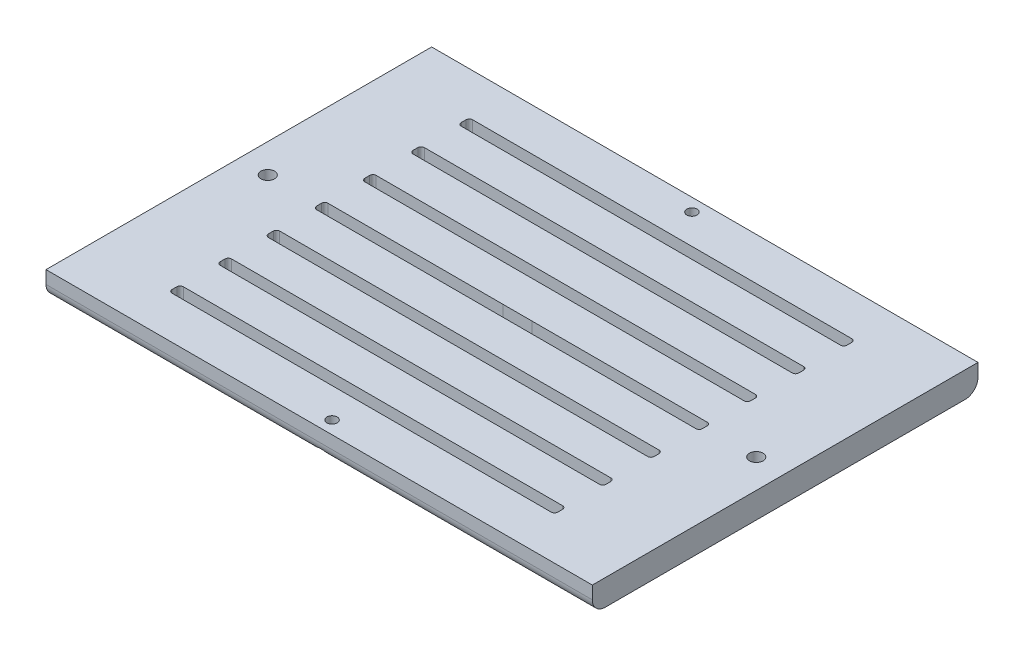
SolidWorks part; units mm, degrees
ref_plane "Ön Düzlem" through (0, 0, 0) normal (0, 0, 1) x (1, 0, 0)
ref_plane "Üst Düzlem" through (0, 0, 0) normal (0, 1, 0) x (1, 0, 0)
ref_plane "Sağ Düzlem" through (0, 0, 0) normal (1, 0, 0) x (0, 0, -1)
sketch "Çizim1" plane through (0, 0, 0) normal (0, 0, 1) x (1, 0, 0)
  line L1 (-85, -4) -> (85, -4)
  line L2 (-85, -4) -> (-85, 4)
  line L3 (-85, 4) -> (85, 4)
  line L4 (85, -4) -> (85, 4)
  line L5 (-85, -4) -> (85, 4) construction
  line L6 (-85, 4) -> (85, -4) construction
  point P0 (0, 0)
  dimension "D1" = 170
  dimension "D2" = 8
extrude "Yükseklik-Ekstrüzyon1" add sketch "Çizim1" along normal mid plane 120 contours L3 L4 L1 L2
sketch "Çizim2" plane through (0, 0, 0) normal (0, 1, 0) x (1, 0, 0)
  line L0 (-85, 60) -> (85, 60) construction
  line L1 (0, 56) -> (0, -56) construction
  line L2 (85, -60) -> (85, 60) construction
  line L3 (-76, 0) -> (76, 0) construction
  line L4 (-85, -60) -> (-85, 60) construction
  circle A0 centre (0, 56) radius 1.6
  circle A1 centre (0, -56) radius 1.6
  circle A2 centre (-76, 0) radius 2.1
  circle A3 centre (76, 0) radius 2.1
  point P4 (0, 0)
  point P8 (0, 60)
  point P13 (0, 0)
  point P16 (85, 0)
  dimension "D2" = 3.2
  dimension "D3" = 4.2
  dimension "D1" = 4
  dimension "D4" = 9
extrude "Kes-Ekstrüzyon1" cut sketch "Çizim2" against normal mid plane 10
sketch "Çizim3" plane through (0, -4, 0) normal (0, -1, 0) x (1, 0, 0)
  circle A0 centre (0, -56) radius 3.4
  circle A1 centre (0, 56) radius 3.4
  circle A2 centre (0, -56) radius 1.6 construction
  circle A3 centre (0, 56) radius 1.6 construction
  circle A4 centre (-76, 0) radius 4.4 construction
  circle A5 centre (76, 0) radius 4.4 construction
  circle A6 centre (76, 0) radius 2.1 construction
  circle A7 centre (-76, 0) radius 2.1 construction
  dimension "D1" = 6.8
  dimension "D2" = 8.8
extrude "Kes-Ekstrüzyon2" cut sketch "Çizim3" against normal blind 2.7
sketch "Çizim4" plane through (0, -4, 0) normal (0, -1, 0) x (1, 0, 0)
  circle A0 centre (-76, 0) radius 4.4
  circle A1 centre (76, 0) radius 4.4
  circle A3 centre (-76, 0) radius 4.4 construction
  circle A4 centre (76, 0) radius 4.4 construction
extrude "Kes-Ekstrüzyon3" cut sketch "Çizim4" against normal blind 3.5
fillet "Radyus1" radius 4 2 edges at (0, -4, -60) (0, -4, 60)
sketch "Çizim5" plane through (0, 0, 0) normal (0, 1, 0) x (1, 0, 0)
  line L0 (0, -5) -> (0, 5) construction
  line L1 (-7.5, 1) -> (7.5, 1)
  line L2 (-7.5, 1) -> (-7.5, -1)
  line L3 (-7.5, -1) -> (7.5, -1)
  line L4 (7.5, 1) -> (7.5, -1)
  line L5 (-7.5, 1) -> (7.5, -1) construction
  line L6 (-7.5, -1) -> (7.5, 1) construction
  line L7 (32.5, 1) -> (32.5, -1)
  line L8 (17.5, -1) -> (32.5, -1)
  line L9 (17.5, 1) -> (17.5, -1)
  line L10 (17.5, 1) -> (32.5, 1)
  line L11 (57.5, 1) -> (57.5, -1)
  line L12 (42.5, -1) -> (57.5, -1)
  line L13 (42.5, 1) -> (42.5, -1)
  line L14 (42.5, 1) -> (57.5, 1)
  line L15 (32.5, 11) -> (32.5, 9)
  line L16 (17.5, 9) -> (32.5, 9)
  line L17 (17.5, 11) -> (17.5, 9)
  line L18 (17.5, 11) -> (32.5, 11)
  line L19 (57.5, 11) -> (57.5, 9)
  line L20 (42.5, 9) -> (57.5, 9)
  line L21 (42.5, 11) -> (42.5, 9)
  line L22 (42.5, 11) -> (57.5, 11)
  line L23 (32.5, 21) -> (32.5, 19)
  line L24 (17.5, 19) -> (32.5, 19)
  line L25 (17.5, 21) -> (17.5, 19)
  line L26 (17.5, 21) -> (32.5, 21)
  line L27 (57.5, 21) -> (57.5, 19)
  line L28 (42.5, 19) -> (57.5, 19)
  line L29 (42.5, 21) -> (42.5, 19)
  line L30 (42.5, 21) -> (57.5, 21)
  line L31 (32.5, 31) -> (32.5, 29)
  line L32 (17.5, 29) -> (32.5, 29)
  line L33 (17.5, 31) -> (17.5, 29)
  line L34 (17.5, 31) -> (32.5, 31)
  line L35 (57.5, 31) -> (57.5, 29)
  line L36 (42.5, 29) -> (57.5, 29)
  line L37 (42.5, 31) -> (42.5, 29)
  line L38 (42.5, 31) -> (57.5, 31)
  line L39 (32.5, 41) -> (32.5, 39)
  line L40 (17.5, 39) -> (32.5, 39)
  line L41 (17.5, 41) -> (17.5, 39)
  line L42 (17.5, 41) -> (32.5, 41)
  line L43 (57.5, 41) -> (57.5, 39)
  line L44 (42.5, 39) -> (57.5, 39)
  line L45 (42.5, 41) -> (42.5, 39)
  line L46 (42.5, 41) -> (57.5, 41)
  line L47 (7.5, 11) -> (7.5, 9)
  line L48 (-7.5, 9) -> (7.5, 9)
  line L49 (-7.5, 11) -> (-7.5, 9)
  line L50 (-7.5, 11) -> (7.5, 11)
  line L51 (7.5, 21) -> (7.5, 19)
  line L52 (-7.5, 19) -> (7.5, 19)
  line L53 (-7.5, 21) -> (-7.5, 19)
  line L54 (-7.5, 21) -> (7.5, 21)
  line L55 (7.5, 31) -> (7.5, 29)
  line L56 (-7.5, 29) -> (7.5, 29)
  line L57 (-7.5, 31) -> (-7.5, 29)
  line L58 (-7.5, 31) -> (7.5, 31)
  line L59 (7.5, 41) -> (7.5, 39)
  line L60 (-7.5, 39) -> (7.5, 39)
  line L61 (-7.5, 41) -> (-7.5, 39)
  line L62 (-7.5, 41) -> (7.5, 41)
  line L63 (-17.5, 1) -> (-17.5, -1)
  line L64 (-32.5, -1) -> (-17.5, -1)
  line L65 (-32.5, 1) -> (-32.5, -1)
  line L66 (-32.5, 1) -> (-17.5, 1)
  line L67 (-42.5, 1) -> (-42.5, -1)
  line L68 (-57.5, -1) -> (-42.5, -1)
  line L69 (-57.5, 1) -> (-57.5, -1)
  line L70 (-57.5, 1) -> (-42.5, 1)
  line L71 (-17.5, 11) -> (-17.5, 9)
  line L72 (-32.5, 9) -> (-17.5, 9)
  line L73 (-32.5, 11) -> (-32.5, 9)
  line L74 (-32.5, 11) -> (-17.5, 11)
  line L75 (-42.5, 11) -> (-42.5, 9)
  line L76 (-57.5, 9) -> (-42.5, 9)
  line L77 (-57.5, 11) -> (-57.5, 9)
  line L78 (-57.5, 11) -> (-42.5, 11)
  line L79 (-17.5, 21) -> (-17.5, 19)
  line L80 (-32.5, 19) -> (-17.5, 19)
  line L81 (-32.5, 21) -> (-32.5, 19)
  line L82 (-32.5, 21) -> (-17.5, 21)
  line L83 (-42.5, 21) -> (-42.5, 19)
  line L84 (-57.5, 19) -> (-42.5, 19)
  line L85 (-57.5, 21) -> (-57.5, 19)
  line L86 (-57.5, 21) -> (-42.5, 21)
  line L87 (-17.5, 31) -> (-17.5, 29)
  line L88 (-32.5, 29) -> (-17.5, 29)
  line L89 (-32.5, 31) -> (-32.5, 29)
  line L90 (-32.5, 31) -> (-17.5, 31)
  line L91 (-42.5, 31) -> (-42.5, 29)
  line L92 (-57.5, 29) -> (-42.5, 29)
  line L93 (-57.5, 31) -> (-57.5, 29)
  line L94 (-57.5, 31) -> (-42.5, 31)
  line L95 (-17.5, 41) -> (-17.5, 39)
  line L96 (-32.5, 39) -> (-17.5, 39)
  line L97 (-32.5, 41) -> (-32.5, 39)
  line L98 (-32.5, 41) -> (-17.5, 41)
  line L99 (-42.5, 41) -> (-42.5, 39)
  line L100 (-57.5, 39) -> (-42.5, 39)
  line L101 (-57.5, 41) -> (-57.5, 39)
  line L102 (-57.5, 41) -> (-42.5, 41)
  line L103 (7.5, 11) -> (7.5, 9)
  line L104 (-7.5, 9) -> (7.5, 9)
  line L105 (-7.5, 11) -> (-7.5, 9)
  line L106 (-7.5, 11) -> (7.5, 11)
  line L107 (7.5, 21) -> (7.5, 19)
  line L108 (-7.5, 19) -> (7.5, 19)
  line L109 (-7.5, 21) -> (-7.5, 19)
  line L110 (-7.5, 21) -> (7.5, 21)
  line L111 (7.5, 31) -> (7.5, 29)
  line L112 (-7.5, 29) -> (7.5, 29)
  line L113 (-7.5, 31) -> (-7.5, 29)
  line L114 (-7.5, 31) -> (7.5, 31)
  line L115 (7.5, 41) -> (7.5, 39)
  line L116 (-7.5, 39) -> (7.5, 39)
  line L117 (-7.5, 41) -> (-7.5, 39)
  line L118 (-7.5, 41) -> (7.5, 41)
  line L119 (7.5, -9) -> (7.5, -11)
  line L120 (-7.5, -11) -> (7.5, -11)
  line L121 (-7.5, -9) -> (-7.5, -11)
  line L122 (-7.5, -9) -> (7.5, -9)
  line L123 (32.5, -9) -> (32.5, -11)
  line L124 (17.5, -11) -> (32.5, -11)
  line L125 (17.5, -9) -> (17.5, -11)
  line L126 (17.5, -9) -> (32.5, -9)
  line L127 (57.5, -9) -> (57.5, -11)
  line L128 (42.5, -11) -> (57.5, -11)
  line L129 (42.5, -9) -> (42.5, -11)
  line L130 (42.5, -9) -> (57.5, -9)
  line L131 (32.5, -19) -> (32.5, -21)
  line L132 (17.5, -21) -> (32.5, -21)
  line L133 (17.5, -19) -> (17.5, -21)
  line L134 (17.5, -19) -> (32.5, -19)
  line L135 (57.5, -19) -> (57.5, -21)
  line L136 (42.5, -21) -> (57.5, -21)
  line L137 (42.5, -19) -> (42.5, -21)
  line L138 (42.5, -19) -> (57.5, -19)
  line L139 (32.5, -29) -> (32.5, -31)
  line L140 (17.5, -31) -> (32.5, -31)
  line L141 (17.5, -29) -> (17.5, -31)
  line L142 (17.5, -29) -> (32.5, -29)
  line L143 (57.5, -29) -> (57.5, -31)
  line L144 (42.5, -31) -> (57.5, -31)
  line L145 (42.5, -29) -> (42.5, -31)
  line L146 (42.5, -29) -> (57.5, -29)
  line L147 (32.5, -39) -> (32.5, -41)
  line L148 (17.5, -41) -> (32.5, -41)
  line L149 (17.5, -39) -> (17.5, -41)
  line L150 (17.5, -39) -> (32.5, -39)
  line L151 (57.5, -39) -> (57.5, -41)
  line L152 (42.5, -41) -> (57.5, -41)
  line L153 (42.5, -39) -> (42.5, -41)
  line L154 (42.5, -39) -> (57.5, -39)
  line L155 (7.5, -19) -> (7.5, -21)
  line L156 (-7.5, -21) -> (7.5, -21)
  line L157 (-7.5, -19) -> (-7.5, -21)
  line L158 (-7.5, -19) -> (7.5, -19)
  line L159 (7.5, -29) -> (7.5, -31)
  line L160 (-7.5, -31) -> (7.5, -31)
  line L161 (-7.5, -29) -> (-7.5, -31)
  line L162 (-7.5, -29) -> (7.5, -29)
  line L163 (7.5, -39) -> (7.5, -41)
  line L164 (-7.5, -41) -> (7.5, -41)
  line L165 (-7.5, -39) -> (-7.5, -41)
  line L166 (-7.5, -39) -> (7.5, -39)
  line L167 (-17.5, -9) -> (-17.5, -11)
  line L168 (-32.5, -11) -> (-17.5, -11)
  line L169 (-32.5, -9) -> (-32.5, -11)
  line L170 (-32.5, -9) -> (-17.5, -9)
  line L171 (-42.5, -9) -> (-42.5, -11)
  line L172 (-57.5, -11) -> (-42.5, -11)
  line L173 (-57.5, -9) -> (-57.5, -11)
  line L174 (-57.5, -9) -> (-42.5, -9)
  line L175 (-17.5, -19) -> (-17.5, -21)
  line L176 (-32.5, -21) -> (-17.5, -21)
  line L177 (-32.5, -19) -> (-32.5, -21)
  line L178 (-32.5, -19) -> (-17.5, -19)
  line L179 (-42.5, -19) -> (-42.5, -21)
  line L180 (-57.5, -21) -> (-42.5, -21)
  line L181 (-57.5, -19) -> (-57.5, -21)
  line L182 (-57.5, -19) -> (-42.5, -19)
  line L183 (-17.5, -29) -> (-17.5, -31)
  line L184 (-32.5, -31) -> (-17.5, -31)
  line L185 (-32.5, -29) -> (-32.5, -31)
  line L186 (-32.5, -29) -> (-17.5, -29)
  line L187 (-42.5, -29) -> (-42.5, -31)
  line L188 (-57.5, -31) -> (-42.5, -31)
  line L189 (-57.5, -29) -> (-57.5, -31)
  line L190 (-57.5, -29) -> (-42.5, -29)
  line L191 (-17.5, -39) -> (-17.5, -41)
  line L192 (-32.5, -41) -> (-17.5, -41)
  line L193 (-32.5, -39) -> (-32.5, -41)
  line L194 (-32.5, -39) -> (-17.5, -39)
  line L195 (-42.5, -39) -> (-42.5, -41)
  line L196 (-57.5, -41) -> (-42.5, -41)
  line L197 (-57.5, -39) -> (-57.5, -41)
  line L198 (-57.5, -39) -> (-42.5, -39)
  line L199 (7.5, -19) -> (7.5, -21)
  line L200 (-7.5, -21) -> (7.5, -21)
  line L201 (-7.5, -19) -> (-7.5, -21)
  line L202 (-7.5, -19) -> (7.5, -19)
  line L203 (7.5, -29) -> (7.5, -31)
  line L204 (-7.5, -31) -> (7.5, -31)
  line L205 (-7.5, -29) -> (-7.5, -31)
  line L206 (-7.5, -29) -> (7.5, -29)
  line L207 (7.5, -39) -> (7.5, -41)
  line L208 (-7.5, -41) -> (7.5, -41)
  line L209 (-7.5, -39) -> (-7.5, -41)
  line L210 (-7.5, -39) -> (7.5, -39)
  line L211 (-42.5, -35) -> (-32.5, -35) construction
  line L212 (-35.4793, -35) -> (-36.4896, -33.25)
  line L213 (-36.4896, -33.25) -> (-38.5104, -33.25)
  line L214 (-38.5104, -33.25) -> (-39.5207, -35)
  line L215 (-39.5207, -35) -> (-38.5104, -36.75)
  line L216 (-38.5104, -36.75) -> (-36.4896, -36.75)
  line L217 (-36.4896, -36.75) -> (-35.4793, -35)
  line L218 (-11.4896, -36.75) -> (-10.4793, -35)
  line L219 (-13.5104, -36.75) -> (-11.4896, -36.75)
  line L220 (-14.5207, -35) -> (-13.5104, -36.75)
  line L221 (-13.5104, -33.25) -> (-14.5207, -35)
  line L222 (-11.4896, -33.25) -> (-13.5104, -33.25)
  line L223 (-10.4793, -35) -> (-11.4896, -33.25)
  line L224 (13.5104, -36.75) -> (14.5207, -35)
  line L225 (11.4896, -36.75) -> (13.5104, -36.75)
  line L226 (10.4793, -35) -> (11.4896, -36.75)
  line L227 (11.4896, -33.25) -> (10.4793, -35)
  line L228 (13.5104, -33.25) -> (11.4896, -33.25)
  line L229 (14.5207, -35) -> (13.5104, -33.25)
  line L230 (38.5104, -36.75) -> (39.5207, -35)
  line L231 (36.4896, -36.75) -> (38.5104, -36.75)
  line L232 (35.4793, -35) -> (36.4896, -36.75)
  line L233 (36.4896, -33.25) -> (35.4793, -35)
  line L234 (38.5104, -33.25) -> (36.4896, -33.25)
  line L235 (39.5207, -35) -> (38.5104, -33.25)
  line L236 (-11.4896, -26.75) -> (-10.4793, -25)
  line L237 (-13.5104, -26.75) -> (-11.4896, -26.75)
  line L238 (-14.5207, -25) -> (-13.5104, -26.75)
  line L239 (-13.5104, -23.25) -> (-14.5207, -25)
  line L240 (-11.4896, -23.25) -> (-13.5104, -23.25)
  line L241 (-10.4793, -25) -> (-11.4896, -23.25)
  line L242 (13.5104, -26.75) -> (14.5207, -25)
  line L243 (11.4896, -26.75) -> (13.5104, -26.75)
  line L244 (10.4793, -25) -> (11.4896, -26.75)
  line L245 (11.4896, -23.25) -> (10.4793, -25)
  line L246 (13.5104, -23.25) -> (11.4896, -23.25)
  line L247 (14.5207, -25) -> (13.5104, -23.25)
  line L248 (38.5104, -26.75) -> (39.5207, -25)
  line L249 (36.4896, -26.75) -> (38.5104, -26.75)
  line L250 (35.4793, -25) -> (36.4896, -26.75)
  line L251 (36.4896, -23.25) -> (35.4793, -25)
  line L252 (38.5104, -23.25) -> (36.4896, -23.25)
  line L253 (39.5207, -25) -> (38.5104, -23.25)
  line L254 (-11.4896, -16.75) -> (-10.4793, -15)
  line L255 (-13.5104, -16.75) -> (-11.4896, -16.75)
  line L256 (-14.5207, -15) -> (-13.5104, -16.75)
  line L257 (-13.5104, -13.25) -> (-14.5207, -15)
  line L258 (-11.4896, -13.25) -> (-13.5104, -13.25)
  line L259 (-10.4793, -15) -> (-11.4896, -13.25)
  line L260 (13.5104, -16.75) -> (14.5207, -15)
  line L261 (11.4896, -16.75) -> (13.5104, -16.75)
  line L262 (10.4793, -15) -> (11.4896, -16.75)
  line L263 (11.4896, -13.25) -> (10.4793, -15)
  line L264 (13.5104, -13.25) -> (11.4896, -13.25)
  line L265 (14.5207, -15) -> (13.5104, -13.25)
  line L266 (38.5104, -16.75) -> (39.5207, -15)
  line L267 (36.4896, -16.75) -> (38.5104, -16.75)
  line L268 (35.4793, -15) -> (36.4896, -16.75)
  line L269 (36.4896, -13.25) -> (35.4793, -15)
  line L270 (38.5104, -13.25) -> (36.4896, -13.25)
  line L271 (39.5207, -15) -> (38.5104, -13.25)
  line L272 (-11.4896, -6.75) -> (-10.4793, -5)
  line L273 (-13.5104, -6.75) -> (-11.4896, -6.75)
  line L274 (-14.5207, -5) -> (-13.5104, -6.75)
  line L275 (-13.5104, -3.25) -> (-14.5207, -5)
  line L276 (-11.4896, -3.25) -> (-13.5104, -3.25)
  line L277 (-10.4793, -5) -> (-11.4896, -3.25)
  line L278 (13.5104, -6.75) -> (14.5207, -5)
  line L279 (11.4896, -6.75) -> (13.5104, -6.75)
  line L280 (10.4793, -5) -> (11.4896, -6.75)
  line L281 (11.4896, -3.25) -> (10.4793, -5)
  line L282 (13.5104, -3.25) -> (11.4896, -3.25)
  line L283 (14.5207, -5) -> (13.5104, -3.25)
  line L284 (38.5104, -6.75) -> (39.5207, -5)
  line L285 (36.4896, -6.75) -> (38.5104, -6.75)
  line L286 (35.4793, -5) -> (36.4896, -6.75)
  line L287 (36.4896, -3.25) -> (35.4793, -5)
  line L288 (38.5104, -3.25) -> (36.4896, -3.25)
  line L289 (39.5207, -5) -> (38.5104, -3.25)
  line L290 (-11.4896, 3.25) -> (-10.4793, 5)
  line L291 (-13.5104, 3.25) -> (-11.4896, 3.25)
  line L292 (-14.5207, 5) -> (-13.5104, 3.25)
  line L293 (-13.5104, 6.75) -> (-14.5207, 5)
  line L294 (-11.4896, 6.75) -> (-13.5104, 6.75)
  line L295 (-10.4793, 5) -> (-11.4896, 6.75)
  line L296 (13.5104, 3.25) -> (14.5207, 5)
  line L297 (11.4896, 3.25) -> (13.5104, 3.25)
  line L298 (10.4793, 5) -> (11.4896, 3.25)
  line L299 (11.4896, 6.75) -> (10.4793, 5)
  line L300 (13.5104, 6.75) -> (11.4896, 6.75)
  line L301 (14.5207, 5) -> (13.5104, 6.75)
  line L302 (38.5104, 3.25) -> (39.5207, 5)
  line L303 (36.4896, 3.25) -> (38.5104, 3.25)
  line L304 (35.4793, 5) -> (36.4896, 3.25)
  line L305 (36.4896, 6.75) -> (35.4793, 5)
  line L306 (38.5104, 6.75) -> (36.4896, 6.75)
  line L307 (39.5207, 5) -> (38.5104, 6.75)
  line L308 (-11.4896, 13.25) -> (-10.4793, 15)
  line L309 (-13.5104, 13.25) -> (-11.4896, 13.25)
  line L310 (-14.5207, 15) -> (-13.5104, 13.25)
  line L311 (-13.5104, 16.75) -> (-14.5207, 15)
  line L312 (-11.4896, 16.75) -> (-13.5104, 16.75)
  line L313 (-10.4793, 15) -> (-11.4896, 16.75)
  line L314 (13.5104, 13.25) -> (14.5207, 15)
  line L315 (11.4896, 13.25) -> (13.5104, 13.25)
  line L316 (10.4793, 15) -> (11.4896, 13.25)
  line L317 (11.4896, 16.75) -> (10.4793, 15)
  line L318 (13.5104, 16.75) -> (11.4896, 16.75)
  line L319 (14.5207, 15) -> (13.5104, 16.75)
  line L320 (38.5104, 13.25) -> (39.5207, 15)
  line L321 (36.4896, 13.25) -> (38.5104, 13.25)
  line L322 (35.4793, 15) -> (36.4896, 13.25)
  line L323 (36.4896, 16.75) -> (35.4793, 15)
  line L324 (38.5104, 16.75) -> (36.4896, 16.75)
  line L325 (39.5207, 15) -> (38.5104, 16.75)
  line L326 (-11.4896, 23.25) -> (-10.4793, 25)
  line L327 (-13.5104, 23.25) -> (-11.4896, 23.25)
  line L328 (-14.5207, 25) -> (-13.5104, 23.25)
  line L329 (-13.5104, 26.75) -> (-14.5207, 25)
  line L330 (-11.4896, 26.75) -> (-13.5104, 26.75)
  line L331 (-10.4793, 25) -> (-11.4896, 26.75)
  line L332 (13.5104, 23.25) -> (14.5207, 25)
  line L333 (11.4896, 23.25) -> (13.5104, 23.25)
  line L334 (10.4793, 25) -> (11.4896, 23.25)
  line L335 (11.4896, 26.75) -> (10.4793, 25)
  line L336 (13.5104, 26.75) -> (11.4896, 26.75)
  line L337 (14.5207, 25) -> (13.5104, 26.75)
  line L338 (38.5104, 23.25) -> (39.5207, 25)
  line L339 (36.4896, 23.25) -> (38.5104, 23.25)
  line L340 (35.4793, 25) -> (36.4896, 23.25)
  line L341 (36.4896, 26.75) -> (35.4793, 25)
  line L342 (38.5104, 26.75) -> (36.4896, 26.75)
  line L343 (39.5207, 25) -> (38.5104, 26.75)
  line L344 (-11.4896, 33.25) -> (-10.4793, 35)
  line L345 (-13.5104, 33.25) -> (-11.4896, 33.25)
  line L346 (-14.5207, 35) -> (-13.5104, 33.25)
  line L347 (-13.5104, 36.75) -> (-14.5207, 35)
  line L348 (-11.4896, 36.75) -> (-13.5104, 36.75)
  line L349 (-10.4793, 35) -> (-11.4896, 36.75)
  line L350 (13.5104, 33.25) -> (14.5207, 35)
  line L351 (11.4896, 33.25) -> (13.5104, 33.25)
  line L352 (10.4793, 35) -> (11.4896, 33.25)
  line L353 (11.4896, 36.75) -> (10.4793, 35)
  line L354 (13.5104, 36.75) -> (11.4896, 36.75)
  line L355 (14.5207, 35) -> (13.5104, 36.75)
  line L356 (38.5104, 33.25) -> (39.5207, 35)
  line L357 (36.4896, 33.25) -> (38.5104, 33.25)
  line L358 (35.4793, 35) -> (36.4896, 33.25)
  line L359 (36.4896, 36.75) -> (35.4793, 35)
  line L360 (38.5104, 36.75) -> (36.4896, 36.75)
  line L361 (39.5207, 35) -> (38.5104, 36.75)
  line L362 (-36.4896, -26.75) -> (-35.4793, -25)
  line L363 (-38.5104, -26.75) -> (-36.4896, -26.75)
  line L364 (-39.5207, -25) -> (-38.5104, -26.75)
  line L365 (-38.5104, -23.25) -> (-39.5207, -25)
  line L366 (-36.4896, -23.25) -> (-38.5104, -23.25)
  line L367 (-35.4793, -25) -> (-36.4896, -23.25)
  line L368 (-36.4896, -16.75) -> (-35.4793, -15)
  line L369 (-38.5104, -16.75) -> (-36.4896, -16.75)
  line L370 (-39.5207, -15) -> (-38.5104, -16.75)
  line L371 (-38.5104, -13.25) -> (-39.5207, -15)
  line L372 (-36.4896, -13.25) -> (-38.5104, -13.25)
  line L373 (-35.4793, -15) -> (-36.4896, -13.25)
  line L374 (-36.4896, -6.75) -> (-35.4793, -5)
  line L375 (-38.5104, -6.75) -> (-36.4896, -6.75)
  line L376 (-39.5207, -5) -> (-38.5104, -6.75)
  line L377 (-38.5104, -3.25) -> (-39.5207, -5)
  line L378 (-36.4896, -3.25) -> (-38.5104, -3.25)
  line L379 (-35.4793, -5) -> (-36.4896, -3.25)
  line L380 (-36.4896, 3.25) -> (-35.4793, 5)
  line L381 (-38.5104, 3.25) -> (-36.4896, 3.25)
  line L382 (-39.5207, 5) -> (-38.5104, 3.25)
  line L383 (-38.5104, 6.75) -> (-39.5207, 5)
  line L384 (-36.4896, 6.75) -> (-38.5104, 6.75)
  line L385 (-35.4793, 5) -> (-36.4896, 6.75)
  line L386 (-36.4896, 13.25) -> (-35.4793, 15)
  line L387 (-38.5104, 13.25) -> (-36.4896, 13.25)
  line L388 (-39.5207, 15) -> (-38.5104, 13.25)
  line L389 (-38.5104, 16.75) -> (-39.5207, 15)
  line L390 (-36.4896, 16.75) -> (-38.5104, 16.75)
  line L391 (-35.4793, 15) -> (-36.4896, 16.75)
  line L392 (-36.4896, 23.25) -> (-35.4793, 25)
  line L393 (-38.5104, 23.25) -> (-36.4896, 23.25)
  line L394 (-39.5207, 25) -> (-38.5104, 23.25)
  line L395 (-38.5104, 26.75) -> (-39.5207, 25)
  line L396 (-36.4896, 26.75) -> (-38.5104, 26.75)
  line L397 (-35.4793, 25) -> (-36.4896, 26.75)
  line L398 (-36.4896, 33.25) -> (-35.4793, 35)
  line L399 (-38.5104, 33.25) -> (-36.4896, 33.25)
  line L400 (-39.5207, 35) -> (-38.5104, 33.25)
  line L401 (-38.5104, 36.75) -> (-39.5207, 35)
  line L402 (-36.4896, 36.75) -> (-38.5104, 36.75)
  line L403 (-35.4793, 35) -> (-36.4896, 36.75)
  circle A0 centre (0, -5) radius 1.75
  circle A1 centre (0, 5) radius 1.75
  circle A2 centre (25, 5) radius 1.75
  circle A3 centre (50, 5) radius 1.75
  circle A4 centre (25, 15) radius 1.75
  circle A5 centre (50, 15) radius 1.75
  circle A6 centre (25, 25) radius 1.75
  circle A7 centre (50, 25) radius 1.75
  circle A8 centre (25, 35) radius 1.75
  circle A9 centre (50, 35) radius 1.75
  circle A10 centre (25, 45) radius 1.75
  circle A11 centre (50, 45) radius 1.75
  circle A12 centre (0, 15) radius 1.75
  circle A13 centre (0, 25) radius 1.75
  circle A14 centre (0, 35) radius 1.75
  circle A15 centre (0, 45) radius 1.75
  circle A16 centre (-25, 5) radius 1.75
  circle A17 centre (-50, 5) radius 1.75
  circle A18 centre (-25, 15) radius 1.75
  circle A19 centre (-50, 15) radius 1.75
  circle A20 centre (-25, 25) radius 1.75
  circle A21 centre (-50, 25) radius 1.75
  circle A22 centre (-25, 35) radius 1.75
  circle A23 centre (-50, 35) radius 1.75
  circle A24 centre (-25, 45) radius 1.75
  circle A25 centre (-50, 45) radius 1.75
  circle A26 centre (0, 15) radius 1.75
  circle A27 centre (0, 25) radius 1.75
  circle A28 centre (0, 35) radius 1.75
  circle A29 centre (0, 45) radius 1.75
  circle A30 centre (0, -15) radius 1.75
  circle A31 centre (25, -15) radius 1.75
  circle A32 centre (50, -15) radius 1.75
  circle A33 centre (25, -25) radius 1.75
  circle A34 centre (50, -25) radius 1.75
  circle A35 centre (25, -35) radius 1.75
  circle A36 centre (50, -35) radius 1.75
  circle A37 centre (25, -45) radius 1.75
  circle A38 centre (50, -45) radius 1.75
  circle A39 centre (0, -25) radius 1.75
  circle A40 centre (0, -35) radius 1.75
  circle A41 centre (0, -45) radius 1.75
  circle A42 centre (-25, -15) radius 1.75
  circle A43 centre (-50, -15) radius 1.75
  circle A44 centre (-25, -25) radius 1.75
  circle A45 centre (-50, -25) radius 1.75
  circle A46 centre (-25, -35) radius 1.75
  circle A47 centre (-50, -35) radius 1.75
  circle A48 centre (-25, -45) radius 1.75
  circle A49 centre (-50, -45) radius 1.75
  circle A50 centre (0, -25) radius 1.75
  circle A51 centre (0, -35) radius 1.75
  circle A52 centre (0, -45) radius 1.75
  circle A53 centre (25, -5) radius 1.75
  circle A54 centre (50, -5) radius 1.75
  circle A55 centre (-25, -5) radius 1.75
  circle A56 centre (-50, -5) radius 1.75
  circle A57 centre (-37.5, -35) radius 1.75 construction
  point P0 (0, 0)
  point P10 (0, 0)
  point P337 (-37.5, -35)
  dimension "D3" = 3.5
  dimension "D7" = 3
  dimension "D11" = 3.5
  dimension "D1" = 2
  dimension "D2" = 15
  dimension "D4" = 10
  dimension "D5" = 5
  dimension "D6" = 5
  dimension "D8" = 2
  dimension "D9" = 4
  dimension "D10" = 4
  dimension "D12" = 8
sketch "Çizim6" plane through (0, 0, 0) normal (0, 1, 0) x (1, 0, 0)
  line L0 (4.5, -43.2492) -> (58.9735, -43.2492)
  line L1 (-59.0265, -1.7492) -> (-4.5, -1.7492)
  line L2 (-60.0265, -0.7492) -> (-60.0265, 0.7508)
  line L3 (-59.0265, 1.7508) -> (-4.5, 1.7508)
  line L4 (59.9735, -0.7492) -> (59.9735, 0.7477)
  line L5 (-60.0265, -1.7492) -> (59.9735, 1.7477) construction
  line L6 (-60.0265, 1.7508) -> (59.9735, -1.7492) construction
  line L7 (4.5, -28.2492) -> (58.9735, -28.2492)
  line L8 (-60.0265, 14.2508) -> (-60.0265, 15.7508)
  line L9 (-59.0265, 13.2508) -> (-4.5, 13.2508)
  line L10 (59.9735, 14.2508) -> (59.9735, 15.7508)
  line L11 (-59.0265, 16.7508) -> (-4.5, 16.7508)
  line L12 (-60.0265, 29.2508) -> (-60.0265, 30.7508)
  line L13 (-59.0265, 28.2508) -> (-4.5, 28.2508)
  line L14 (59.9735, 29.2508) -> (59.9735, 30.7508)
  line L15 (-59.0265, 31.7508) -> (-4.5, 31.7508)
  line L16 (-60.0265, 44.2508) -> (-60.0265, 45.7508)
  line L17 (-59.0265, 43.2508) -> (-4.5, 43.2508)
  line L18 (59.9735, 44.2508) -> (59.9735, 45.7508)
  line L19 (-59.0265, 46.7508) -> (58.9735, 46.7508)
  line L20 (-60.0265, -15.7492) -> (-60.0265, -14.2492)
  line L21 (-59.0265, -16.7492) -> (-4.5, -16.7492)
  line L22 (59.9735, -15.7492) -> (59.9735, -14.2492)
  line L23 (-59.0265, -13.2492) -> (-4.5, -13.2492)
  line L24 (-60.0265, -30.7492) -> (-60.0265, -29.2492)
  line L25 (-59.0265, -31.7492) -> (-4.5, -31.7492)
  line L26 (59.9735, -30.7492) -> (59.9735, -29.2492)
  line L27 (-59.0265, -28.2492) -> (-4.5, -28.2492)
  line L28 (-60.0265, -45.7492) -> (-60.0265, -44.2492)
  line L29 (-59.0265, -46.7492) -> (58.9735, -46.7492)
  line L30 (59.9735, -45.7492) -> (59.9735, -44.2492)
  line L31 (-59.0265, -43.2492) -> (-4.5, -43.2492)
  line L32 (4.5, -31.7492) -> (58.9735, -31.7492)
  line L33 (-2.5, -26.2492) -> (-2.5, -18.7492) construction
  line L34 (2.5, 41.2508) -> (2.5, 33.7508) construction
  line L35 (-2.5, -33.7492) -> (-2.5, -41.2492) construction
  line L36 (-2.5, 41.2508) -> (-2.5, 33.7508) construction
  line L37 (4.5, 43.2508) -> (58.9735, 43.2508)
  line L38 (4.5, 16.7508) -> (58.9735, 16.7508)
  line L39 (2.5, -33.7492) -> (2.5, -41.2492) construction
  line L40 (4.5, -16.7492) -> (58.9735, -16.7492)
  line L41 (4.5, -13.2492) -> (58.9735, -13.2492)
  line L42 (4.5, -1.7492) -> (58.9735, -1.7492)
  line L43 (2.5, -3.7492) -> (2.5, -11.2492) construction
  line L44 (-2.5, -3.7492) -> (-2.5, -11.2492) construction
  line L45 (-2.5, 11.2508) -> (-2.5, 3.7508) construction
  line L46 (2.5, 11.2508) -> (2.5, 3.7507) construction
  line L47 (-2.5, 78.5136) -> (-2.5, -82.0816) construction
  line L48 (2.5, -26.2492) -> (2.5, -18.7492) construction
  line L49 (4.5, 13.2508) -> (58.9735, 13.2508)
  line L50 (4.5, 28.2508) -> (58.9735, 28.2508)
  line L51 (-2.5, 26.2508) -> (-2.5, 18.7508) construction
  line L52 (2.5, 26.2508) -> (2.5, 18.7508) construction
  line L53 (4.5, 31.7508) -> (58.9735, 31.7508)
  line L54 (2.5, 80.6385) -> (2.5, -75.1946) construction
  line L55 (4.4999, 1.7507) -> (58.9735, 1.7477)
  line L56 (-4.5, 43.2508) -> (4.5, 43.2508)
  line L57 (-4.5, 28.2508) -> (4.5, 28.2508)
  line L58 (-4.5, 31.7508) -> (4.5, 31.7508)
  line L59 (-4.5, 13.2508) -> (4.5, 13.2508)
  line L60 (-4.5, 16.7508) -> (4.5, 16.7508)
  line L61 (-4.5, -1.7492) -> (4.5, -1.7492)
  line L62 (-4.5, 1.7508) -> (4.4999, 1.7507)
  line L63 (-4.5, -16.7492) -> (4.5, -16.7492)
  line L64 (-4.5, -13.2492) -> (4.5, -13.2492)
  line L65 (-4.5, -43.2492) -> (4.5, -43.2492)
  line L66 (-4.5, -31.7492) -> (4.5, -31.7492)
  line L67 (-4.5, -28.2492) -> (4.5, -28.2492)
  arc A0 (-4.5, 43.2508) -> (-2.5, 41.2508) centre (-4.5, 41.2508) cw construction
  arc A1 (4.5, 43.2508) -> (2.5, 41.2508) centre (4.5, 41.2508) ccw construction
  arc A2 (2.5, 33.7508) -> (4.5, 31.7508) centre (4.5, 33.7508) ccw construction
  arc A3 (-2.5, 33.7508) -> (-4.5, 31.7508) centre (-4.5, 33.7508) cw construction
  arc A4 (-4.5, 16.7508) -> (-2.5, 18.7508) centre (-4.5, 18.7508) ccw construction
  arc A5 (-4.5, 28.2508) -> (-2.5, 26.2508) centre (-4.5, 26.2508) cw construction
  arc A6 (4.5, 28.2508) -> (2.5, 26.2508) centre (4.5, 26.2508) ccw construction
  arc A7 (4.5, 16.7508) -> (2.5, 18.7508) centre (4.5, 18.7508) cw construction
  arc A8 (4.4999, 1.7507) -> (2.5, 3.7507) centre (4.5, 3.7507) cw construction
  arc A9 (2.5, 11.2508) -> (4.5, 13.2508) centre (4.5, 11.2508) cw construction
  arc A10 (-2.5, 11.2508) -> (-4.5, 13.2508) centre (-4.5, 11.2508) ccw construction
  arc A11 (-4.5, 1.7508) -> (-2.5, 3.7508) centre (-4.5, 3.7508) ccw construction
  arc A12 (-4.5, -13.2492) -> (-2.5, -11.2492) centre (-4.5, -11.2492) ccw construction
  arc A13 (-4.5, -1.7492) -> (-2.5, -3.7492) centre (-4.5, -3.7492) cw construction
  arc A14 (4.5, -1.7492) -> (2.5, -3.7492) centre (4.5, -3.7492) ccw construction
  arc A15 (4.5, -13.2492) -> (2.5, -11.2492) centre (4.5, -11.2492) cw construction
  arc A16 (4.5, -28.2492) -> (2.5, -26.2492) centre (4.5, -26.2492) cw construction
  arc A17 (2.5, -18.7492) -> (4.5, -16.7492) centre (4.5, -18.7492) cw construction
  arc A18 (-2.5, -18.7492) -> (-4.5, -16.7492) centre (-4.5, -18.7492) ccw construction
  arc A19 (-4.5, -28.2492) -> (-2.5, -26.2492) centre (-4.5, -26.2492) ccw construction
  arc A20 (-4.5, -31.7492) -> (-2.5, -33.7492) centre (-4.5, -33.7492) cw construction
  arc A21 (4.5, -31.7492) -> (2.5, -33.7492) centre (4.5, -33.7492) ccw construction
  arc A22 (2.5, -41.2492) -> (4.5, -43.2492) centre (4.5, -41.2492) ccw construction
  arc A23 (-4.5, -43.2492) -> (-2.5, -41.2492) centre (-4.5, -41.2492) ccw construction
  arc A24 (-60.0265, -30.7492) -> (-59.0265, -31.7492) centre (-59.0265, -30.7492) ccw
  arc A25 (-60.0265, -29.2492) -> (-59.0265, -28.2492) centre (-59.0265, -29.2492) cw
  arc A26 (-60.0265, -15.7492) -> (-59.0265, -16.7492) centre (-59.0265, -15.7492) ccw
  arc A27 (-60.0265, -14.2492) -> (-59.0265, -13.2492) centre (-59.0265, -14.2492) cw
  arc A28 (-59.0265, -1.7492) -> (-60.0265, -0.7492) centre (-59.0265, -0.7492) cw
  arc A29 (-60.0265, 0.7508) -> (-59.0265, 1.7508) centre (-59.0265, 0.7508) cw
  arc A30 (-60.0265, 14.2508) -> (-59.0265, 13.2508) centre (-59.0265, 14.2508) ccw
  arc A31 (-60.0265, 15.7508) -> (-59.0265, 16.7508) centre (-59.0265, 15.7508) cw
  arc A32 (-60.0265, 29.2508) -> (-59.0265, 28.2508) centre (-59.0265, 29.2508) ccw
  arc A33 (-60.0265, 30.7508) -> (-59.0265, 31.7508) centre (-59.0265, 30.7508) cw
  arc A34 (-60.0265, 44.2508) -> (-59.0265, 43.2508) centre (-59.0265, 44.2508) ccw
  arc A35 (-60.0265, 45.7508) -> (-59.0265, 46.7508) centre (-59.0265, 45.7508) cw
  arc A36 (59.9735, 45.7508) -> (58.9735, 46.7508) centre (58.9735, 45.7508) ccw
  arc A37 (58.9735, 43.2508) -> (59.9735, 44.2508) centre (58.9735, 44.2508) ccw
  arc A38 (59.9735, 30.7508) -> (58.9735, 31.7508) centre (58.9735, 30.7508) ccw
  arc A39 (58.9735, 28.2508) -> (59.9735, 29.2508) centre (58.9735, 29.2508) ccw
  arc A40 (59.9735, 15.7508) -> (58.9735, 16.7508) centre (58.9735, 15.7508) ccw
  arc A41 (58.9735, 13.2508) -> (59.9735, 14.2508) centre (58.9735, 14.2508) ccw
  arc A42 (58.9735, 1.7477) -> (59.9735, 0.7477) centre (58.9735, 0.7477) cw
  arc A43 (58.9735, -1.7492) -> (59.9735, -0.7492) centre (58.9735, -0.7492) ccw
  arc A44 (59.9735, -14.2492) -> (58.9735, -13.2492) centre (58.9735, -14.2492) ccw
  arc A45 (58.9735, -16.7492) -> (59.9735, -15.7492) centre (58.9735, -15.7492) ccw
  arc A46 (59.9735, -29.2492) -> (58.9735, -28.2492) centre (58.9735, -29.2492) ccw
  arc A47 (58.9735, -31.7492) -> (59.9735, -30.7492) centre (58.9735, -30.7492) ccw
  arc A48 (59.9735, -44.2492) -> (58.9735, -43.2492) centre (58.9735, -44.2492) ccw
  arc A49 (58.9735, -46.7492) -> (59.9735, -45.7492) centre (58.9735, -45.7492) ccw
  arc A50 (-60.0265, -45.7492) -> (-59.0265, -46.7492) centre (-59.0265, -45.7492) ccw
  arc A51 (-60.0265, -44.2492) -> (-59.0265, -43.2492) centre (-59.0265, -44.2492) cw
  point P0 (0, 0)
  point P7 (0, 0)
  point P55 (2.5, 43.2508)
  point P59 (2.5, 31.7508)
  point P69 (-2.5, 28.2508)
  point P72 (2.5, 28.2508)
  point P75 (2.5, 16.7508)
  point P78 (2.5, 1.7508)
  point P81 (2.5, 13.2508)
  point P88 (-2.5, -13.2492)
  point P91 (-2.5, -1.7492)
  point P94 (2.5, -1.7492)
  point P97 (2.5, -13.2492)
  point P102 (2.5, -16.7492)
  point P109 (-2.5, -31.7492)
  point P112 (2.5, -31.7492)
  point P115 (2.5, -43.2492)
  dimension "D6" = 2
  dimension "D7" = 1
  dimension "D1" = 120
  dimension "D2" = 3.5
  dimension "D5" = 5
  dimension "D8" = 2.5
  dimension "D3" = 4
  dimension "D4" = 4
extrude "Kes-Ekstrüzyon4" cut sketch "Çizim6" against normal mid plane 20
